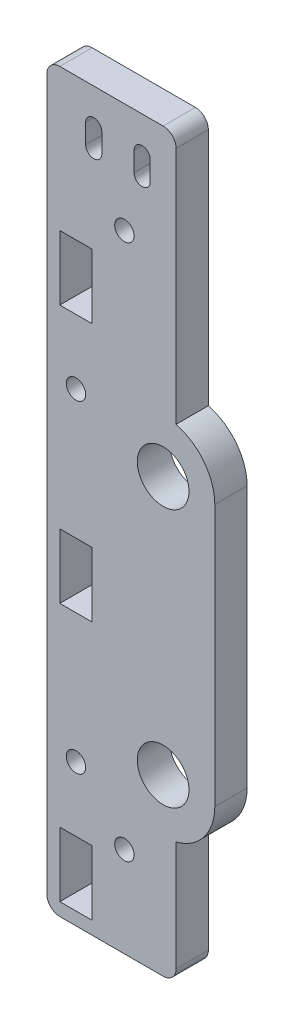
SolidWorks part; units mm, degrees
material "Maple"
ref_plane "Front Plane" through (0, 0, 0) normal (0, 0, 1) x (1, 0, 0)
ref_plane "Top Plane" through (0, 0, 0) normal (0, 1, 0) x (1, 0, 0)
ref_plane "Right Plane" through (0, 0, 0) normal (1, 0, 0) x (0, 0, -1)
sketch "Sketch1" plane through (0, 0, 0) normal (0, 0, 1) x (1, 0, 0)
  line L0 (16, 65) -> (16, 25) construction
  line L1 (0, 0) -> (24, 0)
  line L2 (0, 0) -> (0, 110)
  line L3 (0, 110) -> (24, 110)
  line L4 (24, 0) -> (24, 110)
  line L5 (16, 25) -> (16, 0) construction
  line L6 (10, 0) -> (10, 110) construction
  line L12 (16, 45) -> (24, 45) construction
  line L13 (5.25, 103.5) -> (5.25, 106.5) construction
  line L14 (4, 103.5) -> (4, 106.5)
  line L15 (6.5, 103.5) -> (6.5, 106.5)
  line L16 (12.75, 103.5) -> (12.75, 106.5) construction
  line L17 (11.5, 103.5) -> (11.5, 106.5)
  line L18 (14, 103.5) -> (14, 106.5)
  circle A0 centre (16, 65) radius 4
  circle A1 centre (16, 25) radius 4
  circle A6 centre (10, 12) radius 1.5
  circle A7 centre (10, 95) radius 1.5
  arc A8 (4, 103.5) -> (6.5, 103.5) centre (5.25, 103.5) ccw
  arc A9 (6.5, 106.5) -> (4, 106.5) centre (5.25, 106.5) ccw
  arc A10 (11.5, 103.5) -> (14, 103.5) centre (12.75, 103.5) ccw
  arc A11 (14, 106.5) -> (11.5, 106.5) centre (12.75, 106.5) ccw
  point P30 (5.25, 105)
  point P37 (12.75, 105)
  dimension "D2" = 8
  dimension "D10" = 6
  dimension "D16" = 3
  dimension "D3" = 40
  dimension "D4" = 16
  dimension "D5" = 110
  dimension "D6" = 9.5
  dimension "D7" = 5
  dimension "D8" = 8
  dimension "D9" = 40
  dimension "D11" = 12
  dimension "D12" = 15
  dimension "D13" = 2.5
  dimension "D14" = 3
  dimension "D15" = 5
extrude "Boss-Extrude1" add sketch "Sketch1" along normal blind 5
sketch "Sketch2" plane through (0, 0, 5) normal (0, 0, 1) x (1, 0, 0)
  line L1 (24, 110) -> (18, 110)
  line L2 (24, 110) -> (24, 73)
  line L3 (24, 73) -> (18, 73)
  line L4 (18, 110) -> (18, 73)
  line L5 (24, 0) -> (18, 0)
  line L6 (24, 0) -> (24, 17)
  line L7 (24, 17) -> (18, 17)
  line L8 (18, 0) -> (18, 17)
  dimension "D2" = 17
  dimension "D1" = 6
  dimension "D3" = 37
extrude "Cut-Extrude1" cut sketch "Sketch2" against normal through all
sketch "Sketch3" plane through (0, 0, 5) normal (0, 0, 1) x (1, 0, 0)
  line L3 (18, -2) -> (18, 0)
  line L4 (18, 110) -> (18, 112)
  line L5 (0, 0) -> (18, 0) construction
  line L6 (-2, -2) -> (18, -2)
  line L7 (-2, 112) -> (-2, -2)
  line L8 (18, 112) -> (-2, 112)
  line L9 (-2, -2) -> (18, -2)
  line L10 (-2, 112) -> (-2, -2)
  line L11 (18, 112) -> (-2, 112)
  line L12 (0, 110) -> (0, 0) construction
  line L13 (18, 110) -> (0, 110) construction
  line L14 (0, 0) -> (18, 0)
  line L15 (0, 110) -> (0, 0)
  line L16 (18, 110) -> (0, 110)
  dimension "D1" = 2
extrude "Boss-Extrude2" add sketch "Sketch3" against normal up to surface (5 mm away) up to face at (15, 50, 0)
sketch "Sketch4" plane through (0, 0, 5) normal (0, 0, 1) x (1, 0, 0)
  line L0 (2.5, 20) -> (2.5, 70) construction
  line L1 (0, 0) -> (5, 0)
  line L2 (0, 0) -> (0, 10)
  line L3 (0, 10) -> (5, 10)
  line L4 (5, 0) -> (5, 10)
  line L5 (0, 80) -> (5, 80)
  line L6 (0, 80) -> (0, 90)
  line L7 (0, 90) -> (5, 90)
  line L8 (5, 80) -> (5, 90)
  line L9 (0, 50) -> (5, 50)
  line L10 (0, 50) -> (0, 40)
  line L11 (0, 40) -> (5, 40)
  line L12 (5, 50) -> (5, 40)
  line L13 (0, 45) -> (2.5, 45) construction
  circle A0 centre (2.5, 20) radius 1.5
  circle A1 centre (2.5, 70) radius 1.5
  point P13 (0, 45)
  point P20 (2.5, 50)
  dimension "D5" = 3
  dimension "D1" = 90
  dimension "D2" = 45
  dimension "D3" = 5
  dimension "D4" = 10
  dimension "D6" = 50
extrude "Cut-Extrude2" cut sketch "Sketch4" against normal through all
fillet "Fillet1" radius 2 4 edges at (18, -2, 2.5) (-2, -2, 2.5) (-2, 112, 2.5) (18, 112, 2.5)
fillet "Fillet2" radius 8 2 edges at (24, 17, 2.5) (24, 73, 2.5)
